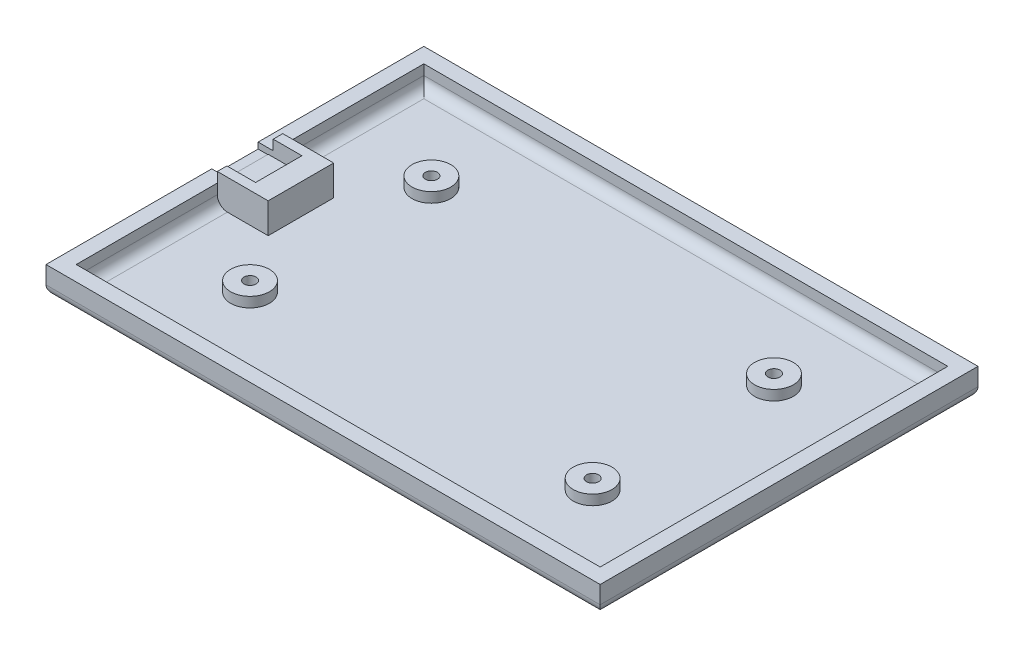
SolidWorks part; units mm, degrees
ref_plane "前视基准面" through (0, 0, 0) normal (0, 0, 1) x (1, 0, 0)
ref_plane "上视基准面" through (0, 0, 0) normal (0, 1, 0) x (1, 0, 0)
ref_plane "右视基准面" through (0, 0, 0) normal (1, 0, 0) x (0, 0, -1)
other "Configuration Table"
sketch "草图1" plane through (0, 0, 0) normal (0, 1, 0) x (1, 0, 0)
  line L1 (-55, 37.5) -> (55, 37.5)
  line L2 (-55, 37.5) -> (-55, -37.5)
  line L3 (-55, -37.5) -> (55, -37.5)
  line L4 (55, 37.5) -> (55, -37.5)
  line L5 (-55, 37.5) -> (55, -37.5) construction
  line L6 (-55, -37.5) -> (55, 37.5) construction
  point P0 (0, 0)
  dimension "D1" = 75
  dimension "D2" = 110
extrude "凸台-拉伸1" add sketch "草图1" along normal blind 1.5
sketch "草图2" plane through (0, 0, 0) normal (0, -1, 0) x (1, 0, 0)
  circle A0 centre (-34, -18) radius 6
  circle A1 centre (-34, 18) radius 6
  circle A2 centre (34, -18) radius 6
  circle A3 centre (34, 18) radius 6
  dimension "D1" = 12
  dimension "D2" = 12
  dimension "D3" = 12
  dimension "D4" = 12
extrude "切除-拉伸1" cut sketch "草图2" against normal blind 0.5
sketch "草图7" plane through (0, 1.5, 0) normal (0, 1, 0) x (1, 0, 0)
  line L0 (-1.925, 0) -> (1.925, 0) construction
  line L1 (0, -1.925) -> (0, 1.925) construction
  circle A0 centre (34, 18) radius 1.2
  circle A1 centre (34, 18) radius 3.85
  circle A2 centre (34, -18) radius 3.85
  circle A3 centre (34, -18) radius 1.2
  circle A4 centre (-34, -18) radius 1.2
  circle A5 centre (-34, -18) radius 3.85
  circle A6 centre (-34, 18) radius 3.85
  circle A7 centre (-34, 18) radius 1.2
  dimension "D1" = 2.4
  dimension "D2" = 7.7
extrude "凸台-拉伸3" add sketch "草图7" along normal blind 2
hole_wizard "ST2.2 十字槽沉头自攻螺钉的锥形沉头孔1" positions "3D草图1" profile "草图8" countersink size "ST2.2" standard "GB" end condition through all
sketch3d "3D草图1"
  line L0 (-34, 0.5, 18) -> (-34, 0, 18) construction
  line L1 (-34, 0.5, -18) -> (-34, 0, -18) construction
  line L2 (34, 0.5, -18) -> (34, 0, -18) construction
  line L3 (34, 0.5, 18) -> (34, 0, 18) construction
  point P0 (-34, 0, 18)
  point P4 (-34, 0, -18)
  point P8 (34, 0, -18)
  point P12 (34, 0, 18)
sketch "草图8" plane through (-34, 0, 18) normal (1, 0, 0) x (0, 0, -1)
  line L0 (0, 0) -> (0, 3.5)
  line L1 (0, 3.5) -> (1.2, 3.5)
  line L2 (1.2, 3.5) -> (1.2, 1)
  line L3 (1.2, 1) -> (2.2, 0)
  line L5 (2.2, 0) -> (0, 0)
  line L6 (-1.2, 1) -> (-2.2, 0) construction
  line L11 (0, -6.35) -> (0, 107.95) construction
  dimension "通孔孔直径" = 2.4
  dimension "通孔孔深度" = 3.5
  dimension "近端锥形沉头孔直径" = 4.4
  dimension "近端锥形沉头孔角度" = 90
sketch "草图9" plane through (0, 1.5, 0) normal (0, 1, 0) x (1, 0, 0)
  line L0 (52, 34.5) -> (-52, 34.5)
  line L1 (-52, 34.5) -> (-52, -34.5)
  line L2 (-52, -34.5) -> (52, -34.5)
  line L3 (52, -34.5) -> (52, 34.5)
  line L4 (55, -37.5) -> (55, 37.5)
  line L5 (55, 37.5) -> (-55, 37.5)
  line L6 (-55, 37.5) -> (-55, -37.5)
  line L7 (-55, -37.5) -> (55, -37.5)
  line L8 (55, -37.5) -> (55, 37.5)
  line L9 (55, 37.5) -> (-55, 37.5)
  line L10 (-55, 37.5) -> (-55, -37.5)
  line L11 (-55, -37.5) -> (55, -37.5)
  dimension "D1" = 0
  dimension "D2" = 3
extrude "凸台-拉伸4" add sketch "草图9" along normal blind 4
fillet "圆角1" radius 2 8 edges at (-55, 0, 0) (0, 0, -37.5) (0, 0, 37.5) (55, 0, 0) (0, 1.5, -34.5) (52, 1.5, 0) (-52, 1.5, 0) (0, 1.5, 34.5)
sketch "草图10" plane through (-55, 0, 0) normal (-1, 0, 0) x (0, 0, 1)
  line L0 (3.5, 4.4) -> (-3.5, 4.4) construction
  line L1 (-4.6, 5.5) -> (4.6, 5.5)
  line L2 (-4.6, 5.5) -> (-4.6, 4.3)
  line L3 (-4.6, 4.3) -> (4.6, 4.3)
  line L4 (4.6, 5.5) -> (4.6, 4.3)
  line L5 (4.6, 5.5) -> (4.6, 7.4) construction
  line L6 (-4.6, 7.4) -> (-4.6, 5.5) construction
  dimension "D1" = 0.1
extrude "切除-拉伸2" cut sketch "草图10" against normal blind 5
sketch "草图11" plane through (0, 1.5, 0) normal (0, 1, 0) x (1, 0, 0)
  line L0 (-53, -35.5) -> (-53, 35.5) construction
  line L1 (-41.9, 6.5) -> (-53, 6.5)
  line L2 (-41.9, 6.5) -> (-41.9, -6.5)
  line L3 (-41.9, -6.5) -> (-53, -6.5)
  line L4 (-53, 6.5) -> (-53, -6.5)
  line L5 (-55, 0) -> (-35.8759, 0) construction
  line L6 (-39.4, 5.8) -> (-39.4, -5.8) construction
  line L8 (-55, 4.6) -> (-55, -4.6) construction
  dimension "D1" = 13
  dimension "D2" = 2.5
extrude "凸台-拉伸5" add sketch "草图11" along normal up to surface (4.4 mm away) from surface starting at face at (0, 0, 0)
sketch "草图12" plane through (0, 4.4, 0) normal (0, 1, 0) x (1, 0, 0)
  line L0 (-46.3, 4.6) -> (-52, 4.6)
  line L2 (-52, 34.5) -> (-52, 4.6) construction
  line L3 (-52, 4.6) -> (-52, 6.5)
  line L4 (-52, 6.5) -> (-41.9, 6.5)
  line L7 (-41.9, -6.5) -> (-52, -6.5)
  line L8 (-52, -6.5) -> (-52, -4.6)
  line L9 (-52, -4.6) -> (-52, -34.5) construction
  line L10 (-52, -4.6) -> (-46.3, -4.6)
  line L12 (-46.3, 4.6) -> (-46.3, -4.6)
  line L13 (-46.5, -4.5) -> (-46.5, 4.5) construction
  line L14 (-53.2, -4.5) -> (-46.5, -4.5) construction
  line L15 (-46.5, 4.5) -> (-53.2, 4.5) construction
  line L17 (-41.9, 6.5) -> (-41.9, -6.5)
  dimension "D1" = 0.2
  dimension "D2" = 0.1
  dimension "D3" = 0.1
extrude "凸台-拉伸6" add sketch "草图12" along normal up to surface (3.1 mm away)
